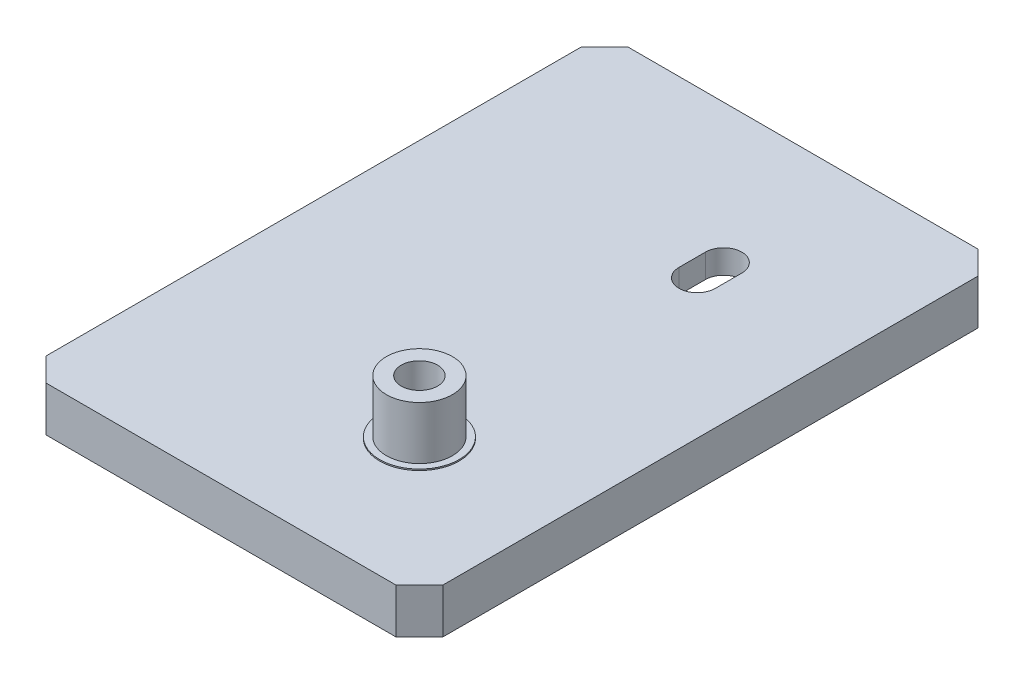
SolidWorks part; units mm, degrees
ref_plane "前视基准面" through (0, 0, 0) normal (0, 0, 1) x (1, 0, 0)
ref_plane "上视基准面" through (0, 0, 0) normal (0, 1, 0) x (1, 0, 0)
ref_plane "右视基准面" through (0, 0, 0) normal (1, 0, 0) x (0, 0, -1)
sketch "草图1" plane through (0, 0, 0) normal (0, 1, 0) x (1, 0, 0)
  line L0 (-58.5815, 0) -> (61.1555, 0) construction
  line L5 (0, 59.114) -> (0, -56.3447) construction
  line L7 (-18, 46) -> (42, 46)
  line L8 (-18, 46) -> (-18, -42)
  line L9 (-18, -42) -> (42, -42)
  line L10 (42, 46) -> (42, -42)
  dimension "D1" = 46
  dimension "D2" = 42
  dimension "D3" = 42
  dimension "D4" = 18
extrude "凸台-拉伸1" add sketch "草图1" along normal blind 6.8
sketch "草图2" plane through (0, 0, 0) normal (0, 1, 0) x (1, 0, 0)
  line L0 (-76.4156, 0) -> (115.4429, 0) construction
  line L1 (0, 65.3547) -> (0, -44.5285) construction
  line L2 (21, 58.9634) -> (21, -44.5285) construction
  line L3 (9.9962, -21) -> (47.8725, -21) construction
  line L4 (-76.4156, -21) -> (47.8725, -21) construction
  line L5 (21, 70.2679) -> (21, -44.5285) construction
  line L6 (8.4771, 21) -> (47.8725, 21) construction
  line L7 (-76.4156, 21) -> (47.8725, 21) construction
  line L8 (-76.4156, 0) -> (47.8725, 0) construction
  line L9 (8.4771, 25) -> (47.8725, 25) construction
  line L10 (21, 21) -> (21, 25) construction
  line L11 (18.25, 21) -> (18.25, 25)
  line L12 (23.75, 21) -> (23.75, 25)
  line L13 (7.2583, 25) -> (47.8725, 25) construction
  line L14 (7.2583, 21) -> (47.8725, 21) construction
  line L15 (0, 70.2679) -> (0, -44.5285) construction
  circle A0 centre (21, -21) radius 2.75
  arc A2 (18.25, 21) -> (23.75, 21) centre (21, 21) ccw
  arc A3 (23.75, 25) -> (18.25, 25) centre (21, 25) ccw
  point P18 (21, 23)
  point P27 (0, 0)
  point P29 (47.8725, -21)
  point P31 (21, 58.9634)
  point P32 (0, 65.3547)
  dimension "D3" = 5.5
  dimension "D6" = 5.5
  dimension "D1" = 21
  dimension "D2" = 21
  dimension "D4" = 21
  dimension "D5" = 4
extrude "切除-拉伸6" cut sketch "草图2" along normal through all
sketch "草图3" plane through (0, 0, 0) normal (0, -1, 0) x (1, 0, 0)
  line L0 (21, -21) -> (21, -25) construction
  line L1 (32.05, -21) -> (32.05, -25)
  line L2 (9.95, -21) -> (9.95, -25)
  circle A0 centre (21, 21) radius 11.05
  arc A1 (32.05, -21) -> (9.95, -21) centre (21, -21) ccw
  arc A2 (9.95, -25) -> (32.05, -25) centre (21, -25) ccw
  point P7 (21, -23)
  dimension "D1" = 22.1
  dimension "D2" = 22.1
extrude "切除-拉伸7" cut sketch "草图3" against normal blind 3.2
sketch "草图4" plane through (0, 6.8, 0) normal (0, 1, 0) x (1, 0, 0)
  circle A0 centre (21, -21) radius 4.99
  circle A1 centre (21, -21) radius 2.75 construction
  circle A2 centre (21, -21) radius 2.75
  dimension "D1" = 9.98
extrude "凸台-拉伸2" add sketch "草图4" along normal blind 8.2
sketch "草图5" plane through (0, 6.8, 0) normal (0, 1, 0) x (1, 0, 0)
  circle A0 centre (21, -21) radius 4
  circle A1 centre (21, -21) radius 6
  dimension "D1" = 8
  dimension "D2" = 12
extrude "轴承限位" add sketch "草图5" along normal blind 0.2
sketch "草图6" plane through (0, 0, 0) normal (0, 1, 0) x (1, 0, 0)
  line L0 (9.9962, -21) -> (47.8725, -21) construction
  line L1 (9.9962, -21) -> (47.8725, -21) construction
  line L2 (-76.4156, 0) -> (115.4429, 0) construction
  line L3 (36.5, 18.3995) -> (36.5, -44.5285) construction
  line L4 (5.5, 65.3547) -> (5.5, -44.5285)
  line L5 (5.5, 18.3995) -> (5.5, -44.5285) construction
  line L6 (-1.4673, -36.5) -> (39.986, -36.5) construction
  line L7 (-1.4673, -36.5) -> (11.7091, -36.5) construction
  line L8 (-1.4673, -5.5) -> (38.9315, -5.5) construction
  line L9 (-1.4673, -5.5) -> (11.7091, -5.5) construction
  line L13 (-76.4156, -36) -> (3.5032, -36) construction
  line L14 (-76.4156, 40) -> (3.5032, 40) construction
  line L15 (-76.4156, 2) -> (3.5032, 2) construction
  line L17 (-13.5, 65.3547) -> (-13.5, -44.5285) construction
  line L18 (-4.5, 65.3547) -> (-4.5, -44.5285)
  line L19 (-4.5, 65.3547) -> (-4.5, -44.5285) construction
  circle A0 centre (5.5, -5.5) radius 1.5
  circle A3 centre (36.5, -5.5) radius 1.5
  circle A4 centre (36.5, -36.5) radius 1.5
  circle A5 centre (5.5, -36.5) radius 1.5
  circle A6 centre (-4.5, 40) radius 1.5
  circle A7 centre (-13.5, 40) radius 1.5
  circle A8 centre (-13.5, 2) radius 1.5
  circle A9 centre (-13.5, -36) radius 1.5
  circle A10 centre (-4.5, 2) radius 1.5
  circle A11 centre (-4.5, -36) radius 1.5
  point P0 (5.5, -5.5)
  point P13 (36.5, -5.5)
  point P19 (-4.5, 40)
  point P23 (36.5, -36.5)
  point P25 (5.5, -36.5)
  point P32 (-13.5, 40)
  point P34 (-13.5, 2)
  point P41 (-13.5, -36)
  point P45 (-4.5, 2)
  point P47 (-4.5, -36)
  dimension "D4" = 3
  dimension "D6" = 3
  dimension "D12" = 3
  dimension "D1" = 5.5
  dimension "D7" = 2
  dimension "D2" = 5.5
  dimension "D3" = 31
  dimension "D5" = 31
  dimension "D8" = 38
  dimension "D9" = 38
  dimension "D10" = 4.5
  dimension "D11" = 9
  dimension "D13" = 2
  dimension "D14" = 3
chamfer "倒角1" distance 3.5355 angle 45 4 edges at (42, 3.4, -46) (42, 3.4, 42) (-18, 3.4, 42) (-18, 3.4, -46)
